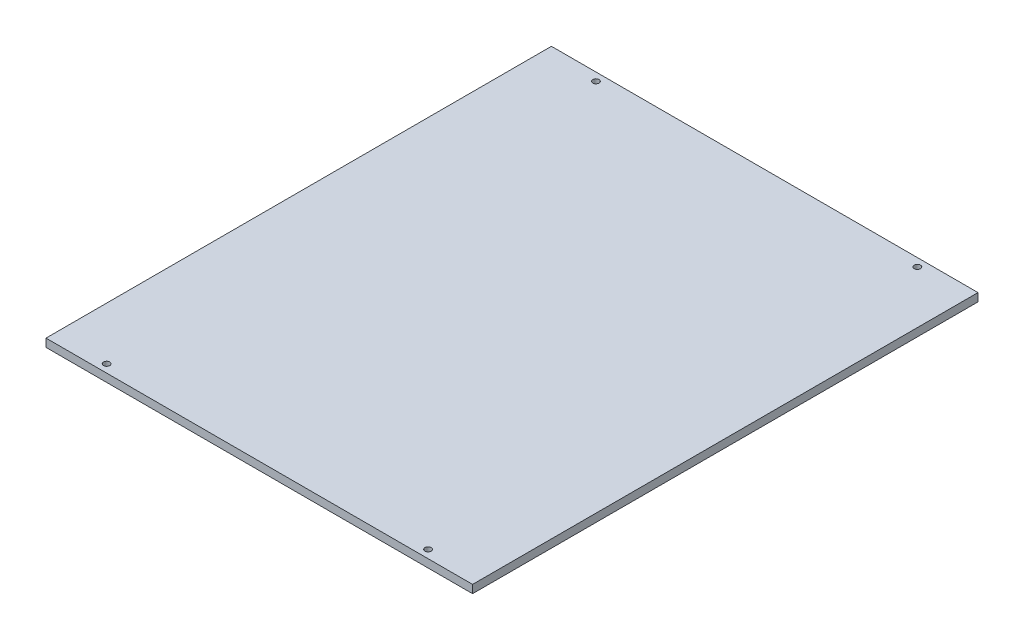
SolidWorks part; units mm, degrees
ref_plane "Front Plane" through (0, 0, 0) normal (0, 0, 1) x (1, 0, 0)
ref_plane "Top Plane" through (0, 0, 0) normal (0, 1, 0) x (1, 0, 0)
ref_plane "Right Plane" through (0, 0, 0) normal (1, 0, 0) x (0, 0, -1)
sketch "Sketch1" plane through (0, 0, 0) normal (0, 1, 0) x (1, 0, 0)
  line L0 (-105.5, 0) -> (-105.5, -250) construction
  line L6 (-211, 0) -> (0, 0)
  line L7 (-211, 0) -> (-211, -250)
  line L16 (-211, -250) -> (0, -250)
  line L21 (0, 0) -> (0, -250)
  line L38 (-211, -125) -> (0, -125) construction
  circle A15 centre (-185, -4) radius 1.55
  circle A16 centre (-185, -246) radius 1.55
  circle A17 centre (-26, -246) radius 1.55
  circle A18 centre (-26, -4) radius 1.55
  point P11 (0, 0)
  dimension "D3" = 3.1
  dimension "D1" = 250
  dimension "D2" = 211
  dimension "D4" = 26
  dimension "D5" = 4
extrude "Boss-Extrude1" add sketch "Sketch1" along normal blind 4
equation "\"cf_tube_outer_diameter\"= 25mm"
equation "\"cf_tube_inner_diameter\" = 21mm"
equation "\"mid_plate_mid_to_top\" = 100mm"
equation "\"mid_plate_mid_to_bottom\" = 30mm"
equation "\"mid_plate_horizontal_spacing\"=250mm"
equation "\"cf_plate_thickness\" =4mm"
equation "\"mid_tube_length\" = 500mm"
equation "\"mid_plate_bottom_width\" = 180mm"
equation "\"mid_support_plate_distance\" = 250mm"
equation "\"nut_strip_2_hole_distance\" = 7mm"
equation "\"nut_strip_hole_diameter\" = 2.5mm"
equation "\"nut_strip_hole_to_edge_distance\"= 2.5mm"
equation "\"D1@Sketch1\"=\"mid_plate_horizontal_spacing\""
equation "\"D1@Boss-Extrude1\"=\"cf_plate_thickness\""
